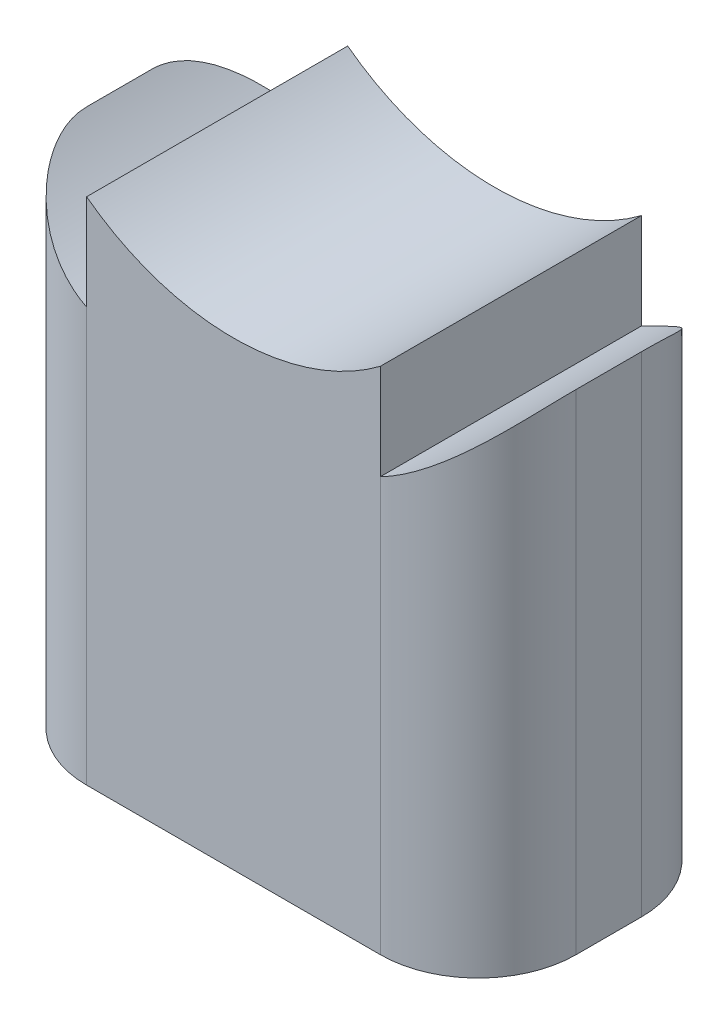
SolidWorks part; units mm, degrees
ref_plane "Alzado" through (0, 0, 0) normal (0, 0, 1) x (1, 0, 0)
ref_plane "Planta" through (0, 0, 0) normal (0, 1, 0) x (1, 0, 0)
ref_plane "Vista lateral" through (0, 0, 0) normal (1, 0, 0) x (0, 0, -1)
sketch "Sketch1" plane through (0, 0, 0) normal (0, 1, 0) x (1, 0, 0)
  line L1 (-45, -40) -> (45, -40)
  line L2 (-75, -10) -> (-75, 10)
  line L3 (-45, 40) -> (45, 40)
  line L4 (75, -10) -> (75, 10)
  line L5 (-75, -40) -> (75, 40) construction
  line L6 (-75, 40) -> (75, -40) construction
  arc A0 (-75, 10) -> (-45, 40) centre (-45, 10) cw
  arc A1 (45, -40) -> (75, -10) centre (45, -10) ccw
  arc A2 (-45, -40) -> (-75, -10) centre (-45, -10) cw
  arc A3 (45, 40) -> (75, 10) centre (45, 10) cw
  point P0 (0, 0)
  dimension "D3" = 30
  dimension "D4" = 30
  dimension "D1" = 150
  dimension "D2" = 80
extrude "Boss-Extrude1" add sketch "Sketch1" along normal blind 150
sketch "Sketch3" plane through (0, 0, 0) normal (0, 0, 1) x (1, 0, 0)
  line L0 (-75, 150) -> (-75, 0)
  line L5 (-75, 0) -> (-45, 0) construction
  line L6 (-75, 0) -> (75, 0)
  line L10 (75, 0) -> (75, 150)
  arc A3 (-75, 150) -> (75, 150) centre (0, 216.1438) ccw
  dimension "D1" = 100
extrude "Cut-Extrude1" cut sketch "Sketch3" against normal through all and the other way through all flip side to cut
sketch "Sketch4" plane through (0, 0, 40) normal (0, 0, 1) x (1, 0, 0)
  point P0 (0, 75)
  dimension "D1" = 75
sketch "Sketch5" plane through (0, 0, 40) normal (0, 0, 1) x (1, 0, 0)
  arc A0 (-45, 126.8409) -> (45, 126.8409) centre (0, 216.1438) ccw construction
  point P0 (0, 216.1438)
ref_axis "Axis1" through (0, 216.1438, 40) along (0, 0, 1)
sketch "Sketch6" plane through (0, 0, 40) normal (0, 0, 1) x (1, 0, 0)
  line L0 (0, 216.1438) -> (0, 116.1438) construction
  line L1 (-45, 126.8409) -> (-45, 156.1438)
  line L3 (45, 156.1438) -> (45, 126.8409)
  arc A0 (-45, 156.1438) -> (45, 156.1438) centre (0, 216.1438) ccw
  arc A1 (-45, 126.8409) -> (45, 126.8409) centre (0, 216.1438) ccw construction
  arc A2 (-45, 126.8409) -> (45, 126.8409) centre (0, 216.1438) ccw
  dimension "D1" = 150
extrude "Boss-Extrude2" add sketch "Sketch6" against normal blind 80
